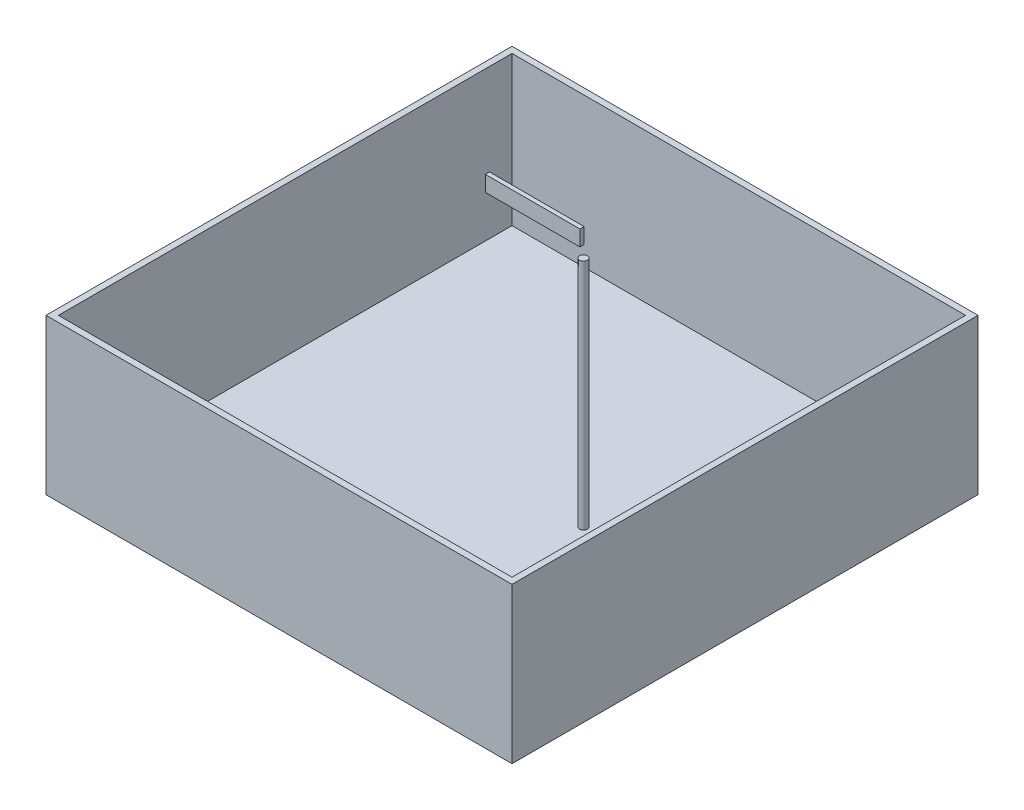
SolidWorks part; units mm, degrees
material "Aleación 1060"
ref_plane "Alzado" through (0, 0, 0) normal (0, 0, 1) x (1, 0, 0)
ref_plane "Planta" through (0, 0, 0) normal (0, 1, 0) x (1, 0, 0)
ref_plane "Vista lateral" through (0, 0, 0) normal (1, 0, 0) x (0, 0, -1)
sketch "Croquis1" plane through (0, 0, 0) normal (0, 0, 1) x (1, 0, 0)
  line L1 (-20, 20) -> (20, 20)
  line L2 (-20, 20) -> (-20, -20)
  line L3 (-20, -20) -> (20, -20)
  line L4 (20, 20) -> (20, -20)
  line L5 (-20, 20) -> (20, -20) construction
  line L6 (-20, -20) -> (20, 20) construction
  point P0 (0, 0)
  dimension "D1" = 40
  dimension "D2" = 40
extrude "Saliente-Extruir1" add sketch "Croquis1" along normal blind 0.3 contours L1 L4 L3 L2
sketch "Croquis2" plane through (0, 0, 0) normal (0, 1, 0) x (1, 0, 0)
  line L0 (0, 0) -> (0, 10) construction
  line L1 (-20, 0) -> (20, 0) construction
  line L2 (-5, 10) -> (-5, 0)
  line L3 (5, 10) -> (5, 0)
  line L4 (-5, 0) -> (5, 0)
  circle A0 centre (0, 10) radius 2.5
  arc A1 (5, 10) -> (-5, 10) centre (0, 10) ccw
  dimension "D2" = 5
  dimension "D3" = 10
  dimension "D1" = 10
extrude "Saliente-Extruir2" add sketch "Croquis2" along normal blind 10 and the other way blind 10
sketch "Croquis3" plane through (0, 0, 0) normal (0, 1, 0) x (1, 0, 0)
  line L1 (-7.0281, 16) -> (7.0281, 16)
  line L2 (-7.0281, 16) -> (-7.0281, 4)
  line L3 (-7.0281, 4) -> (7.0281, 4)
  line L4 (7.0281, 16) -> (7.0281, 4)
  line L5 (-7.0281, 16) -> (7.0281, 4) construction
  line L6 (-7.0281, 4) -> (7.0281, 16) construction
  line L7 (-20, 0) -> (20, 0) construction
  point P0 (0, 10)
  dimension "D1" = 4
extrude "Cortar-Extruir1" cut sketch "Croquis3" against normal blind 2.5 and the other way blind 2.5
sketch "Croquis4" plane through (0, 0, 0.3) normal (0, 0, 1) x (1, 0, 0)
  line L1 (-150, 50) -> (150, 50)
  line L2 (-150, 50) -> (-150, -50)
  line L3 (-150, -50) -> (150, -50)
  line L4 (150, 50) -> (150, -50)
  line L5 (-150, 50) -> (150, -50) construction
  line L6 (-150, -50) -> (150, 50) construction
  point P0 (0, 0)
  dimension "D1" = 100
  dimension "D2" = 300
extrude "Saliente-Extruir3" add sketch "Croquis4" along normal blind 300
shell "Vaciado2" thickness 4 removed face at (0, 50, 150.3)
sketch "Croquis6" plane through (0, 0, 4) normal (0, 0, 1) x (1, 0, 0)
  line L1 (16, 16) -> (-16, 16)
  line L2 (16, 16) -> (16, -16)
  line L3 (16, -16) -> (-16, -16)
  line L4 (-16, 16) -> (-16, -16)
  line L5 (16, 16) -> (-16, -16) construction
  line L6 (16, -16) -> (-16, 16) construction
  point P0 (0, 0)
extrude "Saliente-Extruir4" add sketch "Croquis6" along normal up to vertex (0.3 mm away) up to point (-16, -16, 4.3)
sketch "Croquis7" plane through (0, -46, 0) normal (0, 1, 0) x (1, 0, 0)
  line L0 (0, -4.3) -> (0, -149.3) construction
  line L1 (146, -4.3) -> (-146, -4.3) construction
  line L2 (0, -149.3) -> (45, -149.3) construction
  circle A0 centre (45, -149.3) radius 2.5
  dimension "D3" = 5
  dimension "D1" = 145
  dimension "D2" = 45
extrude "Saliente-Extruir5" add sketch "Croquis7" along normal blind 150 contours A0
sketch "Croquis8" plane through (0, 104, 0) normal (0, 1, 0) x (1, 0, 0)
  line L0 (45, -149.3) -> (45, -144.3) construction
  line L1 (45, -144.3) -> (-23.2022, -144.3) construction
  line L3 (-23.2022, -144.3) -> (37.7358, -144.3)
  line L4 (-23.2022, -144.3) -> (-23.2022, -141.594)
  line L5 (-23.2022, -141.594) -> (37.7358, -141.594)
  line L6 (37.7358, -144.3) -> (37.7358, -141.594)
  dimension "D1" = 5
extrude "Saliente-Extruir6" add sketch "Croquis8" along normal blind 10 separate body contours L5 L6 L3 L4
